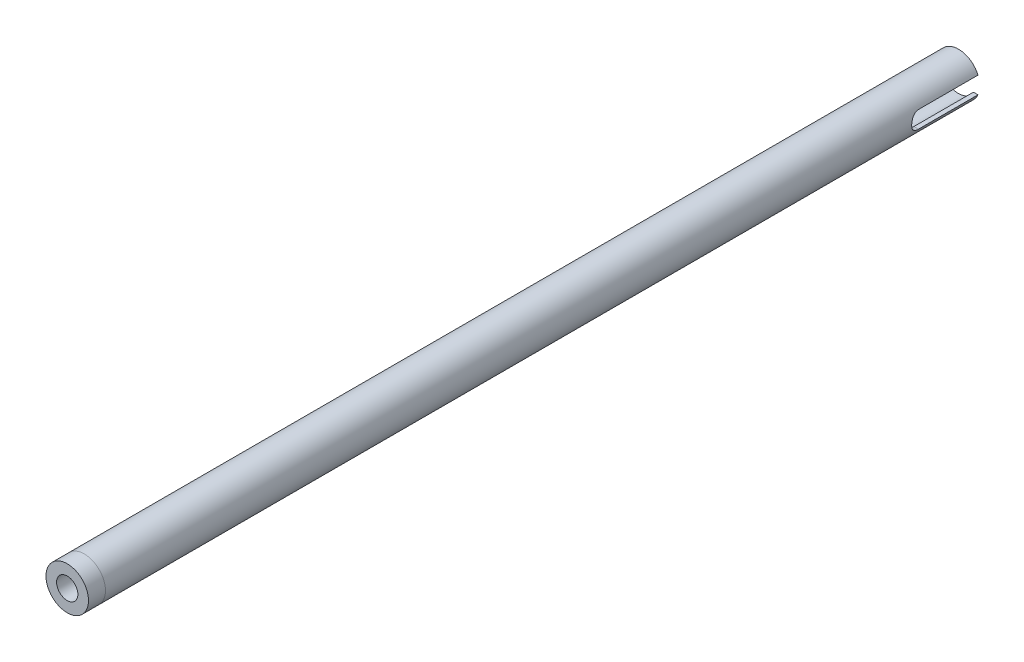
SolidWorks part; units mm, degrees
ref_plane "Front Plane" through (0, 0, 0) normal (0, 0, 1) x (1, 0, 0)
ref_plane "Top Plane" through (0, 0, 0) normal (0, 1, 0) x (1, 0, 0)
ref_plane "Right Plane" through (0, 0, 0) normal (1, 0, 0) x (0, 0, -1)
sketch "Axis" plane through (0, 0, 0) normal (0, 1, 0) x (1, 0, 0)
  line L0 (0, 0) -> (0, 332.6364) construction
  line L1 (0, 0) -> (0, -28.575) construction
  line L2 (0, 332.6364) -> (-7.9375, 332.6364) construction
  line L4 (0, 361.3979) -> (-10.3187, 324.008) construction
  dimension "D1" = 28.575
  dimension "D2" = 7.9375
sketch "Sketch1" plane through (0, 0, 0) normal (0, 0, 1) x (1, 0, 0)
  line L0 (-7.9375, 0) -> (7.9375, 0) construction
  line L1 (-7.2748, 3.175) -> (7.2748, 3.175)
  line L2 (-7.2748, -3.175) -> (7.2748, -3.175)
  circle A0 centre (0, 0) radius 7.9375
  circle A1 centre (0, 0) radius 6.4135
  circle A2 centre (0, 0) radius 3.9688
  dimension "D1" = 15.875
  dimension "D3" = 7.9375
  dimension "D2" = 1.524
  dimension "D4" = 6.35
extrude "Threaded insert 1-1" add sketch "Sketch1" against normal blind 6.35 contours A2 L1 A1 | A1 L1 A0 | A2 L0 A1 L1 | A1 L0 A0 L1 | L0 A1 L2 A0 | L0 A2 L2 A1 | A2 L2 A1 | A1 L2 A0 | L0 A1 L2 A2 | L0 A0 L2 A1 | A0 L0 A1 L1 | A1 L0 A2 L1 region at (4.7887, 1.6543, 0) region at (4.7887, -1.6543, 0) region at (6.9234, 1.6163, 0) region at (6.9234, -1.6163, 0) region at (-4.7887, -1.6543, 0) region at (-4.7887, 1.6543, 0) region at (0, 4.6159, 0) region at (0, -4.6159, 0) region at (0, 6.5666, 0) region at (6.4237, -3.3281, 0) region at (-6.9234, -1.6163, 0) region at (-6.9234, 1.6163, 0)
extrude "Threaded insert 1-2" add sketch "Sketch1<3>" against normal blind 9.525 from surface contours A2 L1 A1 | A2 L0 A1 L1 | L0 A2 L2 A1 | A2 L2 A1 | L0 A1 L2 A2 | A1 L0 A2 L1 region at (4.7887, 1.6543, 0) region at (4.7887, -1.6543, 0) region at (-4.7887, -1.6543, 0) region at (-4.7887, 1.6543, 0) region at (0, 4.6159, 0) region at (0, -4.6159, 0) starting at face at (7.9375, 0, -6.35)
sketch "Sketch1<3>" plane through (0, 0, 0) normal (0, 0, 1) x (1, 0, 0) same geometry as "Sketch1"
extrude "A-arm tube" add sketch "Sketch1<4>" against normal up to vertex (332.6364 mm away) from surface separate body contours A1 L1 A0 | A1 L0 A0 L1 | L0 A1 L2 A0 | A1 L2 A0 | L0 A0 L2 A1 | A0 L0 A1 L1 region at (6.9234, 1.6163, 0) region at (6.9234, -1.6163, 0) region at (0, 6.5666, 0) region at (6.4237, -3.3281, 0) region at (-6.9234, -1.6163, 0) region at (-6.9234, 1.6163, 0) up to point (0, 0, -332.6364) starting at face at (6.4135, 0, -6.35)
sketch "Sketch1<4>" plane through (0, 0, 0) normal (0, 0, 1) x (1, 0, 0) same geometry as "Sketch1"
extrude "Apex slot" cut sketch "Sketch1<5>" along normal blind 25.4 from surface contours A0 L0 A1 L1 | L0 A0 L2 A1 | A1 L0 A0 L1 | L0 A1 L2 A0 region at (6.9234, 1.6163, 0) region at (6.9234, -1.6163, 0) region at (-6.9234, -1.6163, 0) region at (-6.9234, 1.6163, 0) starting at face at (6.4135, 0, -332.6364)
sketch "Sketch1<5>" plane through (0, 0, 0) normal (0, 0, 1) x (1, 0, 0) same geometry as "Sketch1"
fillet "Fillet1" radius 3.175 4 edges at (-6.4237, 3.175, -307.2364) (-6.4237, -3.175, -307.2364) (6.4237, -3.175, -307.2364) (6.4237, 3.175, -307.2364)
equation "\"tube diameter\"= 5 / 8"
equation "\"tube thickness\"= .06"
equation "\"apex thickness\"= .25"
equation "\"tube slot\"= 1"
equation "\"D1@Sketch1\"=\"tube diameter\""
equation "\"D2@Sketch1\"=\"tube thickness\""
equation "\"threaded insert hole\"= .3125"
equation "\"D3@Sketch1\"=\"threaded insert hole\""
equation "\"D4@Sketch1\"=\"apex thickness\""
equation "\"D1@Apex slot\" = \"tube slot\""
equation "\"D1@Fillet1\"=\"apex thickness\"/2"
equation "\"D2@Axis\"=\"tube diameter\"/2"
